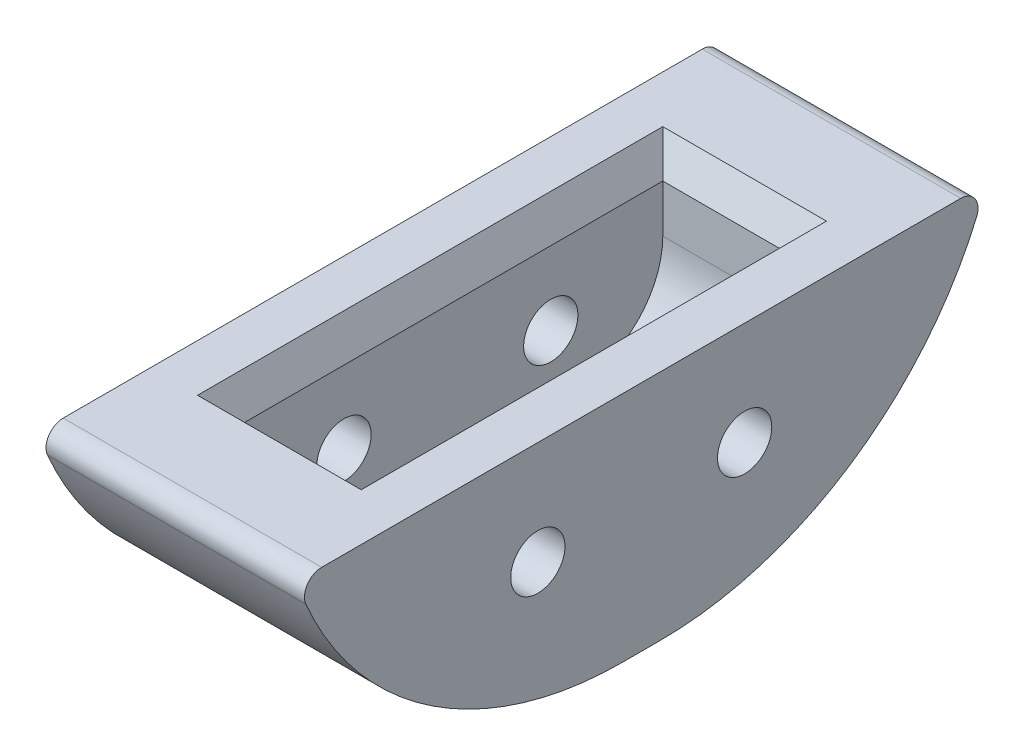
SolidWorks part; units mm, degrees
ref_plane "Front Plane" through (0, 0, 0) normal (0, 0, 1) x (1, 0, 0)
ref_plane "Top Plane" through (0, 0, 0) normal (0, 1, 0) x (1, 0, 0)
ref_plane "Right Plane" through (0, 0, 0) normal (1, 0, 0) x (0, 0, -1)
sketch "Sketch1" plane through (0, 0, 0) normal (0, 1, 0) x (1, 0, 0)
  line L1 (-15, -40) -> (15, -40)
  line L2 (-15, -40) -> (-15, 40)
  line L3 (-15, 40) -> (15, 40)
  line L4 (15, -40) -> (15, 40)
  line L5 (-15, -40) -> (15, 40) construction
  line L6 (-15, 40) -> (15, -40) construction
  point P0 (0, 0)
  dimension "D1" = 30
  dimension "D2" = 80
extrude "Boss-Extrude1" add sketch "Sketch1" along normal blind 27 contours L2 L3 L4 L1
sketch "Sketch2" plane through (15, 0, 0) normal (1, 0, 0) x (0, 0, -1)
  line L0 (-40, 15) -> (40, 15) construction
  line L3 (0, 0) -> (0, 27) construction
  line L4 (-40, 27) -> (40, 27) construction
  circle A0 centre (-12, 15) radius 3.15
  circle A1 centre (12, 15) radius 3.15
  dimension "D1" = 12
  dimension "D3" = 6.3
  dimension "D2" = 12
sketch "Sketch5" plane through (0, 27, 0) normal (0, 1, 0) x (1, 0, 0)
  line L2 (0, -40) -> (0, 40) construction
  line L3 (-15, -40) -> (15, -40) construction
  line L4 (-15, 40) -> (15, 40) construction
  line L5 (-15, 0) -> (15, 0) construction
  line L6 (-15, -40) -> (-15, 40) construction
  line L7 (15, -40) -> (15, 40) construction
  line L9 (-15, -5) -> (15, -5)
  line L10 (-15, -5) -> (-15, 5)
  line L11 (-15, 5) -> (15, 5)
  line L12 (15, -5) -> (15, 5)
  line L13 (-15, -5) -> (15, 5) construction
  line L14 (-15, 5) -> (15, -5) construction
  point P12 (0, 0)
  dimension "D1" = 10
extrude "Boss-Extrude2" add sketch "Sketch5" along normal blind 6
extrude "Cut-Extrude1" cut sketch "Sketch2" against normal blind 40 contours A0 | A1
fillet "Fillet5" radius 40 1 edges at (0, 0, -40)
fillet "Fillet6" radius 40 1 edges at (0, 0, 40)
fillet "Fillet7" radius 2 1 edges at (0, 27, -40)
fillet "Fillet8" radius 2 1 edges at (0, 27, 40)
sketch "Sketch6" plane through (15, 0, 0) normal (1, 0, 0) x (0, 0, -1)
  line L1 (-5, 33) -> (5, 33)
  line L2 (-5, 33) -> (-5, 27)
  line L3 (-5, 27) -> (5, 27)
  line L4 (5, 33) -> (5, 27)
  line L5 (-5, 33) -> (5, 27) construction
  line L6 (-5, 27) -> (5, 33) construction
  point P4 (0, 30)
extrude "Cut-Extrude2" cut sketch "Sketch6" against normal through all
sketch "Sketch7" plane through (0, 27, 0) normal (0, 1, 0) x (1, 0, 0)
  line L1 (7.5, -25) -> (-7.5, -25)
  line L2 (7.5, -25) -> (7.5, 25)
  line L3 (7.5, 25) -> (-7.5, 25)
  line L4 (-7.5, -25) -> (-7.5, 25)
  line L5 (7.5, -25) -> (-7.5, 25) construction
  line L6 (7.5, 25) -> (-7.5, -25) construction
  point P0 (0, 0)
  dimension "D1" = 50
  dimension "D2" = 15
extrude "Cut-Extrude3" cut sketch "Sketch7" against normal blind 19
fillet "Fillet9" radius 10 2 edges at (0, 8, -25) (0, 8, 25)
chamfer "Chamfer1" distance 2 angle 60 4 edges at (0, 27, -25) (7.5, 27, 0) (-7.5, 27, 0) (0, 27, 25) first distance on face at (0, 27, 0)
